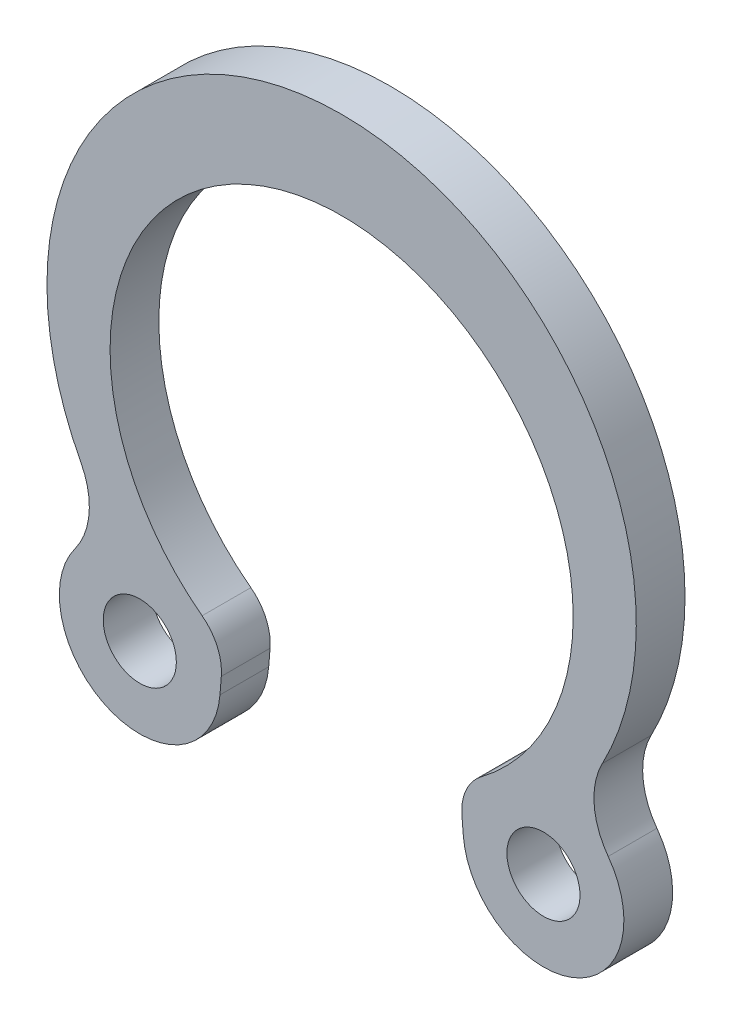
SolidWorks part; units mm, degrees
ref_plane "Спереди" through (0, 0, 0) normal (0, 0, 1) x (1, 0, 0)
ref_plane "Сверху" through (0, 0, 0) normal (0, 1, 0) x (1, 0, 0)
ref_plane "Справа" through (0, 0, 0) normal (1, 0, 0) x (0, 0, -1)
sketch "Эскиз1" plane through (0, 0, 0) normal (0, 0, 1) x (1, 0, 0)
  line L0 (0, -1000) -> (0, 49000) construction
  line L1 (2, -5.0735) -> (2, -4.7286)
  arc A0 (2.4643, -3.8842) -> (0, 4.6) centre (0, 0) ccw
  circle A2 centre (0, 0) radius 5 construction
  circle A3 centre (0, 0) radius 8.8 construction
  circle A4 centre (0, 0) radius 4.75 construction
  circle A5 centre (3.65, -5.0735) radius 0.75
  arc A7 (2, -5.0735) -> (5.04, -4.1844) centre (3.65, -5.0735) ccw
  arc A8 (5.0258, -2.5904) -> (5.04, -4.1844) centre (6.3036, -3.3761) ccw
  arc A9 (2.4643, -3.8842) -> (2, -4.7286) centre (3, -4.7286) ccw
  arc A10 (5.0258, -2.5904) -> (0, 6.4) centre (0, 0.5) ccw
  circle A12 centre (0, 0.5) radius 5.9 construction
  dimension "_d2" = 9.2
  dimension "_d3" = 11.8
  dimension "_d" = 10
  dimension "_D_" = 17.6
  dimension "_d1" = 9.5
  dimension "_d4" = 1.5
  dimension "_a" = 3.3
  dimension "_r1" = 1.5
  dimension "_r2" = 1
  dimension "_e" = 0.5
  dimension "_l" = 2
sketch "Эскиз2" plane through (0, 0, 0) normal (0, 0, 1) x (1, 0, 0)
  line L0 (0, -201000) -> (0, 249000) construction
  line L1 (0, -998.9795) -> (0, 49001.0205) construction
  line L2 (0, 0) -> (2.4643, -3.8842) construction
  line L3 (0, 0) -> (-2.8622, -3.7908) construction
  line L4 (0, 4.75) -> (0, 6.55)
  line L5 (2.4643, -3.8842) -> (2, -4.7286) construction
  line L6 (-2.8622, -3.7908) -> (-2.468, -4.6702) construction
  line L7 (-2.468, -4.6702) -> (-2.4961, -5.0139)
  line L8 (2, -5.0735) -> (2, -4.7286) construction
  line L9 (-5.3482, -2.311) -> (-5.4684, -3.9005) construction
  line L10 (5.0258, -2.5904) -> (5.04, -4.1844) construction
  line L11 (0, 6.55) -> (1, 6.55) construction
  arc A0 (0, 4.75) -> (-2.8622, -3.7908) centre (0, 0) ccw
  circle A1 centre (0, 0) radius 4.75 construction
  circle A2 centre (-4.1406, -4.8801) radius 0.75
  circle A3 centre (3.65, -5.0735) radius 0.75 construction
  arc A4 (-5.4684, -3.9005) -> (-2.4961, -5.0139) centre (-4.1406, -4.8801) ccw
  arc A5 (2, -5.0735) -> (5.04, -4.1844) centre (3.65, -5.0735) ccw construction
  arc A6 (-2.8622, -3.7908) -> (-2.468, -4.6702) centre (-3.4647, -4.5889) cw
  arc A7 (2.4643, -3.8842) -> (2, -4.7286) centre (3, -4.7286) ccw construction
  arc A8 (0, 6.55) -> (-5.3482, -2.311) centre (0, 0.5055) ccw
  arc A9 (-5.4684, -3.9005) -> (-5.3482, -2.311) centre (-6.6754, -3.01) ccw
  arc A10 (5.0258, -2.5904) -> (5.04, -4.1844) centre (6.3036, -3.3761) ccw construction
extrude "Бобышка-Вытянуть1" add sketch "Эскиз2" along normal blind 1
mirror "Зеркальное отражение1" about plane through (0, 4.75, 1) normal (-1, 0, 0) of bodies 103
sketch "Эскиз3" plane through (0, 0, 0) normal (0, 0, 1) x (1, 0, 0)
  circle A0 centre (0, 0) radius 4.75 construction
  circle A1 centre (0, 0) radius 8.8 construction
  circle A2 centre (0, 0) radius 4.75 construction
  circle A3 centre (0, 0) radius 8.8 construction
sketch "Эскиз4" plane through (0, 0, 0) normal (1, 0, 0) x (0, 0, -1)
  line L0 (-1, 6.55) -> (0.2, 6.55)
  point P2 (0, 0)
  dimension "_m" = 1.2
equation "\"D4@Эскиз2\"=\"D1@Эскиз2\"*\"D2@Эскиз2\"/\"D3@Эскиз2\""
equation "\"D1@Бобышка-Вытянуть1\"= \"_s@Эскиз2\""
